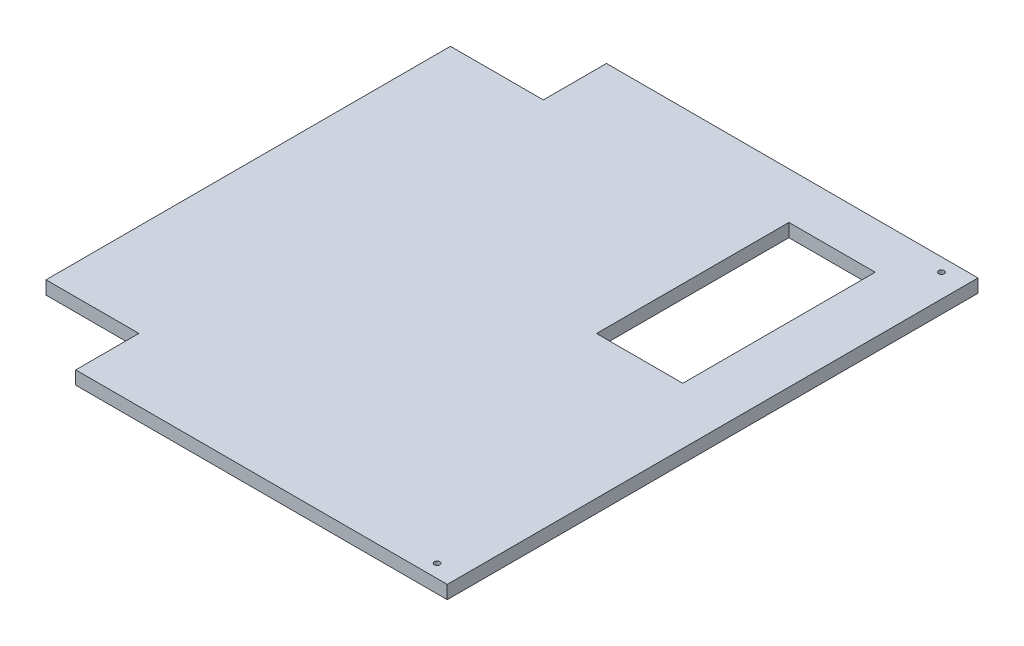
SolidWorks part; units mm, degrees
ref_plane "Front Plane" through (0, 0, 0) normal (0, 0, 1) x (1, 0, 0)
ref_plane "Top Plane" through (0, 0, 0) normal (0, 1, 0) x (1, 0, 0)
ref_plane "Right Plane" through (0, 0, 0) normal (1, 0, 0) x (0, 0, -1)
sketch "Sketch1" plane through (0, 0, 0) normal (0, 1, 0) x (1, 0, 0)
  line L0 (-222.25, 254) -> (222.25, -254) construction
  line L1 (-222.25, 254) -> (222.25, 254)
  line L2 (-222.25, 254) -> (-222.25, -254)
  line L3 (-222.25, -254) -> (222.25, -254)
  line L4 (222.25, 254) -> (222.25, -254)
  dimension "D1" = 508
  dimension "D2" = 444.5
extrude "Boss-Extrude1" add sketch "Sketch1" along normal mid plane 12.7
sketch "Sketch2" plane through (0, 6.35, 0) normal (0, 1, 0) x (1, 0, 0)
  line L10 (222.25, 254) -> (-222.25, 254) construction
  line L11 (-222.25, 254) -> (-133.35, 254)
  line L12 (-222.25, 254) -> (-222.25, 193.548)
  line L13 (-222.25, 193.548) -> (-133.35, 193.548)
  line L14 (-133.35, 254) -> (-133.35, 193.548)
  line L15 (-222.25, 254) -> (-222.25, -254) construction
  dimension "D2" = 88.9
  dimension "D8" = 60.452
extrude "Cut-Extrude1" cut sketch "Sketch2" against normal blind 230.886
mirror "Mirror1" about plane through (0, 0, 0) normal (0, 0, 1) of "Cut-Extrude1"
sketch "Sketch3" plane through (0, 6.35, 0) normal (0, 1, 0) x (1, 0, 0)
  line L0 (-133.35, -254) -> (222.25, -254) construction
  line L1 (222.25, 254) -> (-133.35, 254) construction
  line L2 (222.25, -254) -> (222.25, 254) construction
  line L3 (222.25, -254) -> (222.25, 254) construction
  circle A0 centre (199.898, -241.3) radius 2.667
  circle A20 centre (199.898, 241.3) radius 2.667
  dimension "D1" = 12.7
  dimension "D2" = 12.7
  dimension "D3" = 5.334
  dimension "D4" = 22.352
  dimension "D5" = 22.352
extrude "Cut-Extrude2" cut sketch "Sketch3" against normal blind 230.886
sketch "Sketch4" plane through (0, 6.35, 0) normal (0, 1, 0) x (1, 0, 0)
  line L0 (168.275, 209.55) -> (168.275, 25.4)
  line L1 (168.275, 25.4) -> (85.725, 25.4)
  line L2 (85.725, 25.4) -> (85.725, 209.55)
  line L3 (85.725, 209.55) -> (168.275, 209.55)
  line L4 (222.25, -254) -> (222.25, 254) construction
  line L5 (222.25, 254) -> (-133.35, 254) construction
  dimension "D1" = 184.15
  dimension "D2" = 82.55
  dimension "D3" = 53.975
  dimension "D4" = 44.45
extrude "Cut-Extrude3" cut sketch "Sketch4" against normal up to surface (12.7 mm away) up to face at (199.898, -6.35, 243.967)
